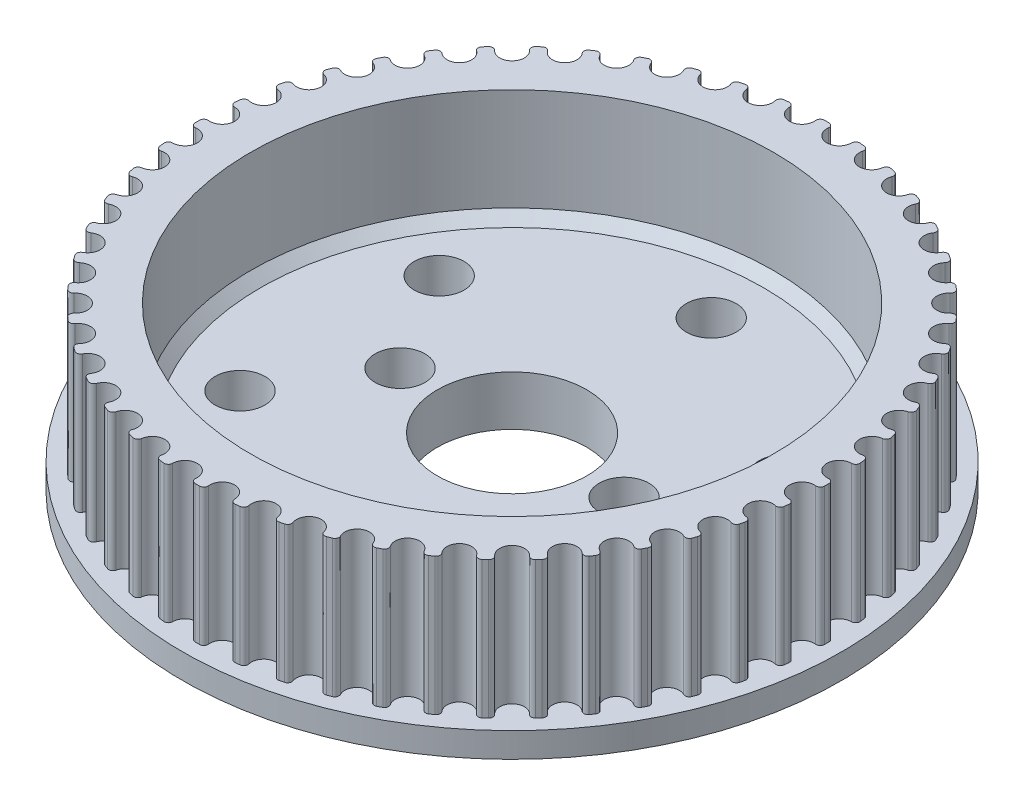
SolidWorks part; units mm, degrees
ref_plane "Front Plane" through (0, 0, 0) normal (0, 0, 1) x (1, 0, 0)
ref_plane "Top Plane" through (0, 0, 0) normal (0, 1, 0) x (1, 0, 0)
ref_plane "Right Plane" through (0, 0, 0) normal (1, 0, 0) x (0, 0, -1)
sketch "Sketch1" plane through (0, 0, 0) normal (0, 1, 0) x (1, 0, 0)
  line L0 (0, 0) -> (40.1263, 0) construction
  line L1 (0, 0) -> (40.0531, 2.4228) construction
  circle A0 centre (0, 0) radius 40.1263 construction
  arc A1 (39.3391, 3.9546) -> (39.529, 0.816) centre (39.3432, 2.3798) ccw
  arc A2 (39.529, 0.816) -> (40.1253, 0.2902) centre (39.5919, 0.2863) cw
  arc A3 (40.1253, 0.2902) -> (40.1263, 0) centre (0, 0) cw
  arc A4 (39.3391, 3.9546) -> (39.8677, 4.5485) centre (39.3377, 4.488) ccw
  arc A5 (39.8677, 4.5485) -> (39.8338, 4.8367) centre (0, 0) ccw
  arc A6 (39.8677, -4.5485) -> (39.8338, -4.8367) centre (0, 0) cw
  arc A7 (39.3391, -3.9546) -> (39.8677, -4.5485) centre (39.3377, -4.488) cw
  arc A8 (39.529, -0.816) -> (39.3391, -3.9546) centre (39.3432, -2.3798) ccw
  arc A9 (39.529, -0.816) -> (40.1253, -0.2902) centre (39.5919, -0.2863) ccw
  arc A10 (40.1253, -0.2902) -> (40.1263, 0) centre (0, 0) ccw
  arc A11 (39.0288, -9.3208) -> (38.9603, -9.6029) centre (0, 0) cw
  arc A12 (38.5756, -8.6676) -> (39.0288, -9.3208) centre (38.51, -9.1969) cw
  arc A13 (39.1424, -5.5748) -> (38.5756, -8.6676) centre (38.7695, -7.1048) ccw
  arc A14 (39.1424, -5.5748) -> (39.7977, -5.1247) centre (39.2687, -5.0565) ccw
  arc A15 (39.7977, -5.1247) -> (39.8338, -4.8367) centre (0, 0) ccw
  arc A16 (37.6207, -13.9573) -> (37.5188, -14.229) centre (0, 0) cw
  arc A17 (37.2496, -13.2542) -> (37.6207, -13.9573) centre (37.1206, -13.7717) cw
  arc A18 (38.1851, -10.2522) -> (37.2496, -13.2542) centre (37.6305, -11.7261) ccw
  arc A19 (38.1851, -10.2522) -> (38.8899, -9.8844) centre (38.3729, -9.753) ccw
  arc A20 (38.8899, -9.8844) -> (38.9603, -9.6029) centre (0, 0) ccw
  arc A21 (35.664, -18.3902) -> (35.5301, -18.6476) centre (0, 0) cw
  arc A22 (35.3804, -17.6475) -> (35.664, -18.3902) centre (35.19, -18.1457) cw
  arc A23 (36.6709, -14.7802) -> (35.3804, -17.6475) centre (35.9427, -16.1765) ccw
  arc A24 (36.6709, -14.7802) -> (37.4149, -14.5) centre (36.9175, -14.3072) ccw
  arc A25 (37.4149, -14.5) -> (37.5188, -14.229) centre (0, 0) ccw
  arc A26 (33.1873, -22.5549) -> (33.0233, -22.7944) centre (0, 0) cw
  arc A27 (32.9953, -21.7834) -> (33.1873, -22.5549) centre (32.7462, -22.2551) cw
  arc A28 (34.622, -19.0926) -> (32.9953, -21.7834) centre (33.7307, -20.3909) ccw
  arc A29 (34.622, -19.0926) -> (35.3943, -18.9041) centre (34.9238, -18.6528) ccw
  arc A30 (35.3943, -18.9041) -> (35.5301, -18.6476) centre (0, 0) ccw
  arc A31 (30.2266, -26.3908) -> (30.035, -26.6087) centre (0, 0) cw
  arc A32 (30.129, -25.6018) -> (30.2266, -26.3908) centre (29.8248, -26.04) cw
  arc A33 (32.0682, -23.1266) -> (30.129, -25.6018) centre (31.0269, -24.3081) ccw
  arc A34 (32.0682, -23.1266) -> (32.8576, -23.0326) centre (32.4208, -22.7264) ccw
  arc A35 (32.8576, -23.0326) -> (33.0233, -22.7944) centre (0, 0) ccw
  arc A36 (26.8252, -29.8418) -> (26.6087, -30.035) centre (0, 0) cw
  arc A37 (26.8234, -29.0467) -> (26.8252, -29.8418) centre (26.4686, -29.4451) cw
  arc A38 (29.0467, -26.8234) -> (26.8234, -29.0467) centre (27.8707, -27.8707) ccw
  arc A39 (29.0467, -26.8234) -> (29.8418, -26.8252) centre (29.4451, -26.4686) ccw
  arc A40 (29.8418, -26.8252) -> (30.035, -26.6087) centre (0, 0) ccw
  arc A41 (23.0326, -32.8576) -> (22.7944, -33.0233) centre (0, 0) cw
  arc A42 (23.1266, -32.0682) -> (23.0326, -32.8576) centre (22.7264, -32.4208) cw
  arc A43 (25.6018, -30.129) -> (23.1266, -32.0682) centre (24.3081, -31.0269) ccw
  arc A44 (25.6018, -30.129) -> (26.3908, -30.2266) centre (26.04, -29.8248) ccw
  arc A45 (26.3908, -30.2266) -> (26.6087, -30.035) centre (0, 0) ccw
  arc A46 (18.9041, -35.3943) -> (18.6476, -35.5301) centre (0, 0) cw
  arc A47 (19.0926, -34.622) -> (18.9041, -35.3943) centre (18.6528, -34.9238) cw
  arc A48 (21.7834, -32.9953) -> (19.0926, -34.622) centre (20.3909, -33.7307) ccw
  arc A49 (21.7834, -32.9953) -> (22.5549, -33.1873) centre (22.2551, -32.7462) ccw
  arc A50 (22.5549, -33.1873) -> (22.7944, -33.0233) centre (0, 0) ccw
  arc A51 (14.5, -37.4149) -> (14.229, -37.5188) centre (0, 0) cw
  arc A52 (14.7802, -36.6709) -> (14.5, -37.4149) centre (14.3072, -36.9175) cw
  arc A53 (17.6475, -35.3804) -> (14.7802, -36.6709) centre (16.1765, -35.9427) ccw
  arc A54 (17.6475, -35.3804) -> (18.3902, -35.664) centre (18.1457, -35.19) ccw
  arc A55 (18.3902, -35.664) -> (18.6476, -35.5301) centre (0, 0) ccw
  arc A56 (9.8844, -38.8899) -> (9.6029, -38.9603) centre (0, 0) cw
  arc A57 (10.2522, -38.1851) -> (9.8844, -38.8899) centre (9.753, -38.3729) cw
  arc A58 (13.2542, -37.2496) -> (10.2522, -38.1851) centre (11.7261, -37.6305) ccw
  arc A59 (13.2542, -37.2496) -> (13.9573, -37.6207) centre (13.7717, -37.1206) ccw
  arc A60 (13.9573, -37.6207) -> (14.229, -37.5188) centre (0, 0) ccw
  arc A61 (5.1247, -39.7977) -> (4.8367, -39.8338) centre (0, 0) cw
  arc A62 (5.5748, -39.1424) -> (5.1247, -39.7977) centre (5.0565, -39.2687) cw
  arc A63 (8.6676, -38.5756) -> (5.5748, -39.1424) centre (7.1048, -38.7695) ccw
  arc A64 (8.6676, -38.5756) -> (9.3208, -39.0288) centre (9.1969, -38.51) ccw
  arc A65 (9.3208, -39.0288) -> (9.6029, -38.9603) centre (0, 0) ccw
  arc A66 (0.2902, -40.1253) -> (0, -40.1263) centre (0, 0) cw
  arc A67 (0.816, -39.529) -> (0.2902, -40.1253) centre (0.2863, -39.5919) cw
  arc A68 (3.9546, -39.3391) -> (0.816, -39.529) centre (2.3798, -39.3432) ccw
  arc A69 (3.9546, -39.3391) -> (4.5485, -39.8677) centre (4.488, -39.3377) ccw
  arc A70 (4.5485, -39.8677) -> (4.8367, -39.8338) centre (0, 0) ccw
  arc A71 (-4.5485, -39.8677) -> (-4.8367, -39.8338) centre (0, 0) cw
  arc A72 (-3.9546, -39.3391) -> (-4.5485, -39.8677) centre (-4.488, -39.3377) cw
  arc A73 (-0.816, -39.529) -> (-3.9546, -39.3391) centre (-2.3798, -39.3432) ccw
  arc A74 (-0.816, -39.529) -> (-0.2902, -40.1253) centre (-0.2863, -39.5919) ccw
  arc A75 (-0.2902, -40.1253) -> (0, -40.1263) centre (0, 0) ccw
  arc A76 (-9.3208, -39.0288) -> (-9.6029, -38.9603) centre (0, 0) cw
  arc A77 (-8.6676, -38.5756) -> (-9.3208, -39.0288) centre (-9.1969, -38.51) cw
  arc A78 (-5.5748, -39.1424) -> (-8.6676, -38.5756) centre (-7.1048, -38.7695) ccw
  arc A79 (-5.5748, -39.1424) -> (-5.1247, -39.7977) centre (-5.0565, -39.2687) ccw
  arc A80 (-5.1247, -39.7977) -> (-4.8367, -39.8338) centre (0, 0) ccw
  arc A81 (-13.9573, -37.6207) -> (-14.229, -37.5188) centre (0, 0) cw
  arc A82 (-13.2542, -37.2496) -> (-13.9573, -37.6207) centre (-13.7717, -37.1206) cw
  arc A83 (-10.2522, -38.1851) -> (-13.2542, -37.2496) centre (-11.7261, -37.6305) ccw
  arc A84 (-10.2522, -38.1851) -> (-9.8844, -38.8899) centre (-9.753, -38.3729) ccw
  arc A85 (-9.8844, -38.8899) -> (-9.6029, -38.9603) centre (0, 0) ccw
  arc A86 (-18.3902, -35.664) -> (-18.6476, -35.5301) centre (0, 0) cw
  arc A87 (-17.6475, -35.3804) -> (-18.3902, -35.664) centre (-18.1457, -35.19) cw
  arc A88 (-14.7802, -36.6709) -> (-17.6475, -35.3804) centre (-16.1765, -35.9427) ccw
  arc A89 (-14.7802, -36.6709) -> (-14.5, -37.4149) centre (-14.3072, -36.9175) ccw
  arc A90 (-14.5, -37.4149) -> (-14.229, -37.5188) centre (0, 0) ccw
  arc A91 (-22.5549, -33.1873) -> (-22.7944, -33.0233) centre (0, 0) cw
  arc A92 (-21.7834, -32.9953) -> (-22.5549, -33.1873) centre (-22.2551, -32.7462) cw
  arc A93 (-19.0926, -34.622) -> (-21.7834, -32.9953) centre (-20.3909, -33.7307) ccw
  arc A94 (-19.0926, -34.622) -> (-18.9041, -35.3943) centre (-18.6528, -34.9238) ccw
  arc A95 (-18.9041, -35.3943) -> (-18.6476, -35.5301) centre (0, 0) ccw
  arc A96 (-26.3908, -30.2266) -> (-26.6087, -30.035) centre (0, 0) cw
  arc A97 (-25.6018, -30.129) -> (-26.3908, -30.2266) centre (-26.04, -29.8248) cw
  arc A98 (-23.1266, -32.0682) -> (-25.6018, -30.129) centre (-24.3081, -31.0269) ccw
  arc A99 (-23.1266, -32.0682) -> (-23.0326, -32.8576) centre (-22.7264, -32.4208) ccw
  arc A100 (-23.0326, -32.8576) -> (-22.7944, -33.0233) centre (0, 0) ccw
  arc A101 (-29.8418, -26.8252) -> (-30.035, -26.6087) centre (0, 0) cw
  arc A102 (-29.0467, -26.8234) -> (-29.8418, -26.8252) centre (-29.4451, -26.4686) cw
  arc A103 (-26.8234, -29.0467) -> (-29.0467, -26.8234) centre (-27.8707, -27.8707) ccw
  arc A104 (-26.8234, -29.0467) -> (-26.8252, -29.8418) centre (-26.4686, -29.4451) ccw
  arc A105 (-26.8252, -29.8418) -> (-26.6087, -30.035) centre (0, 0) ccw
  arc A106 (-32.8576, -23.0326) -> (-33.0233, -22.7944) centre (0, 0) cw
  arc A107 (-32.0682, -23.1266) -> (-32.8576, -23.0326) centre (-32.4208, -22.7264) cw
  arc A108 (-30.129, -25.6018) -> (-32.0682, -23.1266) centre (-31.0269, -24.3081) ccw
  arc A109 (-30.129, -25.6018) -> (-30.2266, -26.3908) centre (-29.8248, -26.04) ccw
  arc A110 (-30.2266, -26.3908) -> (-30.035, -26.6087) centre (0, 0) ccw
  arc A111 (-35.3943, -18.9041) -> (-35.5301, -18.6476) centre (0, 0) cw
  arc A112 (-34.622, -19.0926) -> (-35.3943, -18.9041) centre (-34.9238, -18.6528) cw
  arc A113 (-32.9953, -21.7834) -> (-34.622, -19.0926) centre (-33.7307, -20.3909) ccw
  arc A114 (-32.9953, -21.7834) -> (-33.1873, -22.5549) centre (-32.7462, -22.2551) ccw
  arc A115 (-33.1873, -22.5549) -> (-33.0233, -22.7944) centre (0, 0) ccw
  arc A116 (-37.4149, -14.5) -> (-37.5188, -14.229) centre (0, 0) cw
  arc A117 (-36.6709, -14.7802) -> (-37.4149, -14.5) centre (-36.9175, -14.3072) cw
  arc A118 (-35.3804, -17.6475) -> (-36.6709, -14.7802) centre (-35.9427, -16.1765) ccw
  arc A119 (-35.3804, -17.6475) -> (-35.664, -18.3902) centre (-35.19, -18.1457) ccw
  arc A120 (-35.664, -18.3902) -> (-35.5301, -18.6476) centre (0, 0) ccw
  arc A121 (-38.8899, -9.8844) -> (-38.9603, -9.6029) centre (0, 0) cw
  arc A122 (-38.1851, -10.2522) -> (-38.8899, -9.8844) centre (-38.3729, -9.753) cw
  arc A123 (-37.2496, -13.2542) -> (-38.1851, -10.2522) centre (-37.6305, -11.7261) ccw
  arc A124 (-37.2496, -13.2542) -> (-37.6207, -13.9573) centre (-37.1206, -13.7717) ccw
  arc A125 (-37.6207, -13.9573) -> (-37.5188, -14.229) centre (0, 0) ccw
  arc A126 (-39.7977, -5.1247) -> (-39.8338, -4.8367) centre (0, 0) cw
  arc A127 (-39.1424, -5.5748) -> (-39.7977, -5.1247) centre (-39.2687, -5.0565) cw
  arc A128 (-38.5756, -8.6676) -> (-39.1424, -5.5748) centre (-38.7695, -7.1048) ccw
  arc A129 (-38.5756, -8.6676) -> (-39.0288, -9.3208) centre (-38.51, -9.1969) ccw
  arc A130 (-39.0288, -9.3208) -> (-38.9603, -9.6029) centre (0, 0) ccw
  arc A131 (-40.1253, -0.2902) -> (-40.1263, 0) centre (0, 0) cw
  arc A132 (-39.529, -0.816) -> (-40.1253, -0.2902) centre (-39.5919, -0.2863) cw
  arc A133 (-39.3391, -3.9546) -> (-39.529, -0.816) centre (-39.3432, -2.3798) ccw
  arc A134 (-39.3391, -3.9546) -> (-39.8677, -4.5485) centre (-39.3377, -4.488) ccw
  arc A135 (-39.8677, -4.5485) -> (-39.8338, -4.8367) centre (0, 0) ccw
  arc A136 (-39.8677, 4.5485) -> (-39.8338, 4.8367) centre (0, 0) cw
  arc A137 (-39.3391, 3.9546) -> (-39.8677, 4.5485) centre (-39.3377, 4.488) cw
  arc A138 (-39.529, 0.816) -> (-39.3391, 3.9546) centre (-39.3432, 2.3798) ccw
  arc A139 (-39.529, 0.816) -> (-40.1253, 0.2902) centre (-39.5919, 0.2863) ccw
  arc A140 (-40.1253, 0.2902) -> (-40.1263, 0) centre (0, 0) ccw
  arc A141 (-39.0288, 9.3208) -> (-38.9603, 9.6029) centre (0, 0) cw
  arc A142 (-38.5756, 8.6676) -> (-39.0288, 9.3208) centre (-38.51, 9.1969) cw
  arc A143 (-39.1424, 5.5748) -> (-38.5756, 8.6676) centre (-38.7695, 7.1048) ccw
  arc A144 (-39.1424, 5.5748) -> (-39.7977, 5.1247) centre (-39.2687, 5.0565) ccw
  arc A145 (-39.7977, 5.1247) -> (-39.8338, 4.8367) centre (0, 0) ccw
  arc A146 (-37.6207, 13.9573) -> (-37.5188, 14.229) centre (0, 0) cw
  arc A147 (-37.2496, 13.2542) -> (-37.6207, 13.9573) centre (-37.1206, 13.7717) cw
  arc A148 (-38.1851, 10.2522) -> (-37.2496, 13.2542) centre (-37.6305, 11.7261) ccw
  arc A149 (-38.1851, 10.2522) -> (-38.8899, 9.8844) centre (-38.3729, 9.753) ccw
  arc A150 (-38.8899, 9.8844) -> (-38.9603, 9.6029) centre (0, 0) ccw
  arc A151 (-35.664, 18.3902) -> (-35.5301, 18.6476) centre (0, 0) cw
  arc A152 (-35.3804, 17.6475) -> (-35.664, 18.3902) centre (-35.19, 18.1457) cw
  arc A153 (-36.6709, 14.7802) -> (-35.3804, 17.6475) centre (-35.9427, 16.1765) ccw
  arc A154 (-36.6709, 14.7802) -> (-37.4149, 14.5) centre (-36.9175, 14.3072) ccw
  arc A155 (-37.4149, 14.5) -> (-37.5188, 14.229) centre (0, 0) ccw
  arc A156 (-33.1873, 22.5549) -> (-33.0233, 22.7944) centre (0, 0) cw
  arc A157 (-32.9953, 21.7834) -> (-33.1873, 22.5549) centre (-32.7462, 22.2551) cw
  arc A158 (-34.622, 19.0926) -> (-32.9953, 21.7834) centre (-33.7307, 20.3909) ccw
  arc A159 (-34.622, 19.0926) -> (-35.3943, 18.9041) centre (-34.9238, 18.6528) ccw
  arc A160 (-35.3943, 18.9041) -> (-35.5301, 18.6476) centre (0, 0) ccw
  arc A161 (-30.2266, 26.3908) -> (-30.035, 26.6087) centre (0, 0) cw
  arc A162 (-30.129, 25.6018) -> (-30.2266, 26.3908) centre (-29.8248, 26.04) cw
  arc A163 (-32.0682, 23.1266) -> (-30.129, 25.6018) centre (-31.0269, 24.3081) ccw
  arc A164 (-32.0682, 23.1266) -> (-32.8576, 23.0326) centre (-32.4208, 22.7264) ccw
  arc A165 (-32.8576, 23.0326) -> (-33.0233, 22.7944) centre (0, 0) ccw
  arc A166 (-26.8252, 29.8418) -> (-26.6087, 30.035) centre (0, 0) cw
  arc A167 (-26.8234, 29.0467) -> (-26.8252, 29.8418) centre (-26.4686, 29.4451) cw
  arc A168 (-29.0467, 26.8234) -> (-26.8234, 29.0467) centre (-27.8707, 27.8707) ccw
  arc A169 (-29.0467, 26.8234) -> (-29.8418, 26.8252) centre (-29.4451, 26.4686) ccw
  arc A170 (-29.8418, 26.8252) -> (-30.035, 26.6087) centre (0, 0) ccw
  arc A171 (-23.0326, 32.8576) -> (-22.7944, 33.0233) centre (0, 0) cw
  arc A172 (-23.1266, 32.0682) -> (-23.0326, 32.8576) centre (-22.7264, 32.4208) cw
  arc A173 (-25.6018, 30.129) -> (-23.1266, 32.0682) centre (-24.3081, 31.0269) ccw
  arc A174 (-25.6018, 30.129) -> (-26.3908, 30.2266) centre (-26.04, 29.8248) ccw
  arc A175 (-26.3908, 30.2266) -> (-26.6087, 30.035) centre (0, 0) ccw
  arc A176 (-18.9041, 35.3943) -> (-18.6476, 35.5301) centre (0, 0) cw
  arc A177 (-19.0926, 34.622) -> (-18.9041, 35.3943) centre (-18.6528, 34.9238) cw
  arc A178 (-21.7834, 32.9953) -> (-19.0926, 34.622) centre (-20.3909, 33.7307) ccw
  arc A179 (-21.7834, 32.9953) -> (-22.5549, 33.1873) centre (-22.2551, 32.7462) ccw
  arc A180 (-22.5549, 33.1873) -> (-22.7944, 33.0233) centre (0, 0) ccw
  arc A181 (-14.5, 37.4149) -> (-14.229, 37.5188) centre (0, 0) cw
  arc A182 (-14.7802, 36.6709) -> (-14.5, 37.4149) centre (-14.3072, 36.9175) cw
  arc A183 (-17.6475, 35.3804) -> (-14.7802, 36.6709) centre (-16.1765, 35.9427) ccw
  arc A184 (-17.6475, 35.3804) -> (-18.3902, 35.664) centre (-18.1457, 35.19) ccw
  arc A185 (-18.3902, 35.664) -> (-18.6476, 35.5301) centre (0, 0) ccw
  arc A186 (-9.8844, 38.8899) -> (-9.6029, 38.9603) centre (0, 0) cw
  arc A187 (-10.2522, 38.1851) -> (-9.8844, 38.8899) centre (-9.753, 38.3729) cw
  arc A188 (-13.2542, 37.2496) -> (-10.2522, 38.1851) centre (-11.7261, 37.6305) ccw
  arc A189 (-13.2542, 37.2496) -> (-13.9573, 37.6207) centre (-13.7717, 37.1206) ccw
  arc A190 (-13.9573, 37.6207) -> (-14.229, 37.5188) centre (0, 0) ccw
  arc A191 (-5.1247, 39.7977) -> (-4.8367, 39.8338) centre (0, 0) cw
  arc A192 (-5.5748, 39.1424) -> (-5.1247, 39.7977) centre (-5.0565, 39.2687) cw
  arc A193 (-8.6676, 38.5756) -> (-5.5748, 39.1424) centre (-7.1048, 38.7695) ccw
  arc A194 (-8.6676, 38.5756) -> (-9.3208, 39.0288) centre (-9.1969, 38.51) ccw
  arc A195 (-9.3208, 39.0288) -> (-9.6029, 38.9603) centre (0, 0) ccw
  arc A196 (-0.2902, 40.1253) -> (0, 40.1263) centre (0, 0) cw
  arc A197 (-0.816, 39.529) -> (-0.2902, 40.1253) centre (-0.2863, 39.5919) cw
  arc A198 (-3.9546, 39.3391) -> (-0.816, 39.529) centre (-2.3798, 39.3432) ccw
  arc A199 (-3.9546, 39.3391) -> (-4.5485, 39.8677) centre (-4.488, 39.3377) ccw
  arc A200 (-4.5485, 39.8677) -> (-4.8367, 39.8338) centre (0, 0) ccw
  arc A201 (4.5485, 39.8677) -> (4.8367, 39.8338) centre (0, 0) cw
  arc A202 (3.9546, 39.3391) -> (4.5485, 39.8677) centre (4.488, 39.3377) cw
  arc A203 (0.816, 39.529) -> (3.9546, 39.3391) centre (2.3798, 39.3432) ccw
  arc A204 (0.816, 39.529) -> (0.2902, 40.1253) centre (0.2863, 39.5919) ccw
  arc A205 (0.2902, 40.1253) -> (0, 40.1263) centre (0, 0) ccw
  arc A206 (9.3208, 39.0288) -> (9.6029, 38.9603) centre (0, 0) cw
  arc A207 (8.6676, 38.5756) -> (9.3208, 39.0288) centre (9.1969, 38.51) cw
  arc A208 (5.5748, 39.1424) -> (8.6676, 38.5756) centre (7.1048, 38.7695) ccw
  arc A209 (5.5748, 39.1424) -> (5.1247, 39.7977) centre (5.0565, 39.2687) ccw
  arc A210 (5.1247, 39.7977) -> (4.8367, 39.8338) centre (0, 0) ccw
  arc A211 (13.9573, 37.6207) -> (14.229, 37.5188) centre (0, 0) cw
  arc A212 (13.2542, 37.2496) -> (13.9573, 37.6207) centre (13.7717, 37.1206) cw
  arc A213 (10.2522, 38.1851) -> (13.2542, 37.2496) centre (11.7261, 37.6305) ccw
  arc A214 (10.2522, 38.1851) -> (9.8844, 38.8899) centre (9.753, 38.3729) ccw
  arc A215 (9.8844, 38.8899) -> (9.6029, 38.9603) centre (0, 0) ccw
  arc A216 (18.3902, 35.664) -> (18.6476, 35.5301) centre (0, 0) cw
  arc A217 (17.6475, 35.3804) -> (18.3902, 35.664) centre (18.1457, 35.19) cw
  arc A218 (14.7802, 36.6709) -> (17.6475, 35.3804) centre (16.1765, 35.9427) ccw
  arc A219 (14.7802, 36.6709) -> (14.5, 37.4149) centre (14.3072, 36.9175) ccw
  arc A220 (14.5, 37.4149) -> (14.229, 37.5188) centre (0, 0) ccw
  arc A221 (22.5549, 33.1873) -> (22.7944, 33.0233) centre (0, 0) cw
  arc A222 (21.7834, 32.9953) -> (22.5549, 33.1873) centre (22.2551, 32.7462) cw
  arc A223 (19.0926, 34.622) -> (21.7834, 32.9953) centre (20.3909, 33.7307) ccw
  arc A224 (19.0926, 34.622) -> (18.9041, 35.3943) centre (18.6528, 34.9238) ccw
  arc A225 (18.9041, 35.3943) -> (18.6476, 35.5301) centre (0, 0) ccw
  arc A226 (26.3908, 30.2266) -> (26.6087, 30.035) centre (0, 0) cw
  arc A227 (25.6018, 30.129) -> (26.3908, 30.2266) centre (26.04, 29.8248) cw
  arc A228 (23.1266, 32.0682) -> (25.6018, 30.129) centre (24.3081, 31.0269) ccw
  arc A229 (23.1266, 32.0682) -> (23.0326, 32.8576) centre (22.7264, 32.4208) ccw
  arc A230 (23.0326, 32.8576) -> (22.7944, 33.0233) centre (0, 0) ccw
  arc A231 (29.8418, 26.8252) -> (30.035, 26.6087) centre (0, 0) cw
  arc A232 (29.0467, 26.8234) -> (29.8418, 26.8252) centre (29.4451, 26.4686) cw
  arc A233 (26.8234, 29.0467) -> (29.0467, 26.8234) centre (27.8707, 27.8707) ccw
  arc A234 (26.8234, 29.0467) -> (26.8252, 29.8418) centre (26.4686, 29.4451) ccw
  arc A235 (26.8252, 29.8418) -> (26.6087, 30.035) centre (0, 0) ccw
  arc A236 (32.8576, 23.0326) -> (33.0233, 22.7944) centre (0, 0) cw
  arc A237 (32.0682, 23.1266) -> (32.8576, 23.0326) centre (32.4208, 22.7264) cw
  arc A238 (30.129, 25.6018) -> (32.0682, 23.1266) centre (31.0269, 24.3081) ccw
  arc A239 (30.129, 25.6018) -> (30.2266, 26.3908) centre (29.8248, 26.04) ccw
  arc A240 (30.2266, 26.3908) -> (30.035, 26.6087) centre (0, 0) ccw
  arc A241 (35.3943, 18.9041) -> (35.5301, 18.6476) centre (0, 0) cw
  arc A242 (34.622, 19.0926) -> (35.3943, 18.9041) centre (34.9238, 18.6528) cw
  arc A243 (32.9953, 21.7834) -> (34.622, 19.0926) centre (33.7307, 20.3909) ccw
  arc A244 (32.9953, 21.7834) -> (33.1873, 22.5549) centre (32.7462, 22.2551) ccw
  arc A245 (33.1873, 22.5549) -> (33.0233, 22.7944) centre (0, 0) ccw
  arc A246 (37.4149, 14.5) -> (37.5188, 14.229) centre (0, 0) cw
  arc A247 (36.6709, 14.7802) -> (37.4149, 14.5) centre (36.9175, 14.3072) cw
  arc A248 (35.3804, 17.6475) -> (36.6709, 14.7802) centre (35.9427, 16.1765) ccw
  arc A249 (35.3804, 17.6475) -> (35.664, 18.3902) centre (35.19, 18.1457) ccw
  arc A250 (35.664, 18.3902) -> (35.5301, 18.6476) centre (0, 0) ccw
  arc A251 (38.8899, 9.8844) -> (38.9603, 9.6029) centre (0, 0) cw
  arc A252 (38.1851, 10.2522) -> (38.8899, 9.8844) centre (38.3729, 9.753) cw
  arc A253 (37.2496, 13.2542) -> (38.1851, 10.2522) centre (37.6305, 11.7261) ccw
  arc A254 (37.2496, 13.2542) -> (37.6207, 13.9573) centre (37.1206, 13.7717) ccw
  arc A255 (37.6207, 13.9573) -> (37.5188, 14.229) centre (0, 0) ccw
  arc A256 (39.7977, 5.1247) -> (39.8338, 4.8367) centre (0, 0) cw
  arc A257 (39.1424, 5.5748) -> (39.7977, 5.1247) centre (39.2687, 5.0565) cw
  arc A258 (38.5756, 8.6676) -> (39.1424, 5.5748) centre (38.7695, 7.1048) ccw
  arc A259 (38.5756, 8.6676) -> (39.0288, 9.3208) centre (38.51, 9.1969) ccw
  arc A260 (39.0288, 9.3208) -> (38.9603, 9.6029) centre (0, 0) ccw
  point P23 (37.7713, 2.2847)
  point P44 (0, 0)
  dimension "D1" = 80.2527
  dimension "D3" = 1.5748
  dimension "D4" = 0.5334
  dimension "D2" = 3.462
  dimension "D5" = 2.286
  dimension "D6" = 52
extrude "Boss-Extrude1" add sketch "Sketch1" along normal blind 17.5 contours A79 A80 A71 A72 A73 A74 A75 A66 A67 A68 A69 A70 A61 A62 A63 A64 A65 A56 A57 A58 A59 A60 A51 A52 A53 A54 A55 A46 A47 A48 A49 A50 A41 A42 A43 A44 A45 A36 A37 A38 A39 A40 A31 A32 A33 A34 A35 A26 A27 A28 A29 region at (0, 0, 0)
sketch "Sketch2" plane through (0, 0, 0) normal (0, -1, 0) x (1, 0, 0)
  circle A1 centre (0, 0) radius 33.3375
  circle A2 centre (0, 0) radius 40.1263 construction
  circle A3 centre (0, 0) radius 42.0313
  circle A4 centre (0, 0) radius 9.525
  dimension "D1" = 80.2527
  dimension "D2" = 66.675
  dimension "D4" = 19.05
  dimension "D3" = 1.905
extrude "Cut-Extrude1" cut sketch "Sketch2" against normal through all contours A1 A4 | A4 region at (-32.3946, 0, 0) region at (0, 0, 0)
extrude "Boss-Extrude2" add sketch "Sketch2<3>" along normal blind 3.175 contours A1 A4 | A3 A1 region at (-32.3946, 0, 0) region at (-40.8425, 0, 0)
sketch "Sketch2<3>" plane through (0, 0, 0) normal (0, -1, 0) x (1, 0, 0) same geometry as "Sketch2"
extrude "Boss-Extrude3" add sketch "Sketch2<4>" against normal blind 3.175 contours A1 A4 region at (-32.3946, 0, 0)
sketch "Sketch2<4>" plane through (0, 0, 0) normal (0, -1, 0) x (1, 0, 0) same geometry as "Sketch2"
sketch "Sketch3" plane through (0, -3.175, 0) normal (0, -1, 0) x (1, 0, 0)
  circle A0 centre (21.997, 12.7) radius 3.175 construction
  circle A1 centre (0, 25.4) radius 3.175 construction
  circle A2 centre (21.997, -12.7) radius 3.175 construction
  circle A3 centre (0, -25.4) radius 3.175 construction
  circle A4 centre (-21.997, 12.7) radius 3.175 construction
  circle A5 centre (-21.997, -12.7) radius 3.175 construction
  circle A6 centre (21.997, 12.7) radius 3.175
  circle A7 centre (0, 25.4) radius 3.175
  circle A8 centre (21.997, -12.7) radius 3.175
  circle A9 centre (0, -25.4) radius 3.175
  circle A10 centre (-21.997, 12.7) radius 3.175
  circle A11 centre (-21.997, -12.7) radius 3.175
  circle A18 centre (14.2875, 0) radius 3.8735 construction
  circle A19 centre (-14.2875, 0) radius 3.8735 construction
  circle A20 centre (14.2875, 0) radius 3.8735 construction
  circle A21 centre (-14.2875, 0) radius 3.8735 construction
  circle A22 centre (14.2875, 0) radius 3.175
  circle A23 centre (-14.2875, 0) radius 3.175
  dimension "D1" = 6.35
extrude "Cut-Extrude2" cut sketch "Sketch3" against normal through all
chamfer "Chamfer1" distance 1.27 1 edges at (0, 3.175, -33.3375)
equation "\"T\" = 52"
equation "\"P\"= 5mm * \"TolRatio\""
equation "\"PD\"= \"T\" * \"P\" / PI"
equation "\"Angle\"= 360 / \"T\""
equation "\"D1@Sketch1\"=\"PD\""
equation "\"D2@Sketch1\"=\"Angle\"/2"
equation "\"D6@Sketch1\"=\"T\""
equation "\"W\" = 15mm + 2.5mm"
equation "\"D1@Boss-Extrude1\"=\"W\""
equation "\"TolRatio\"= 32 / 33"
equation "\"D1@Sketch2\"=\"PD\""
